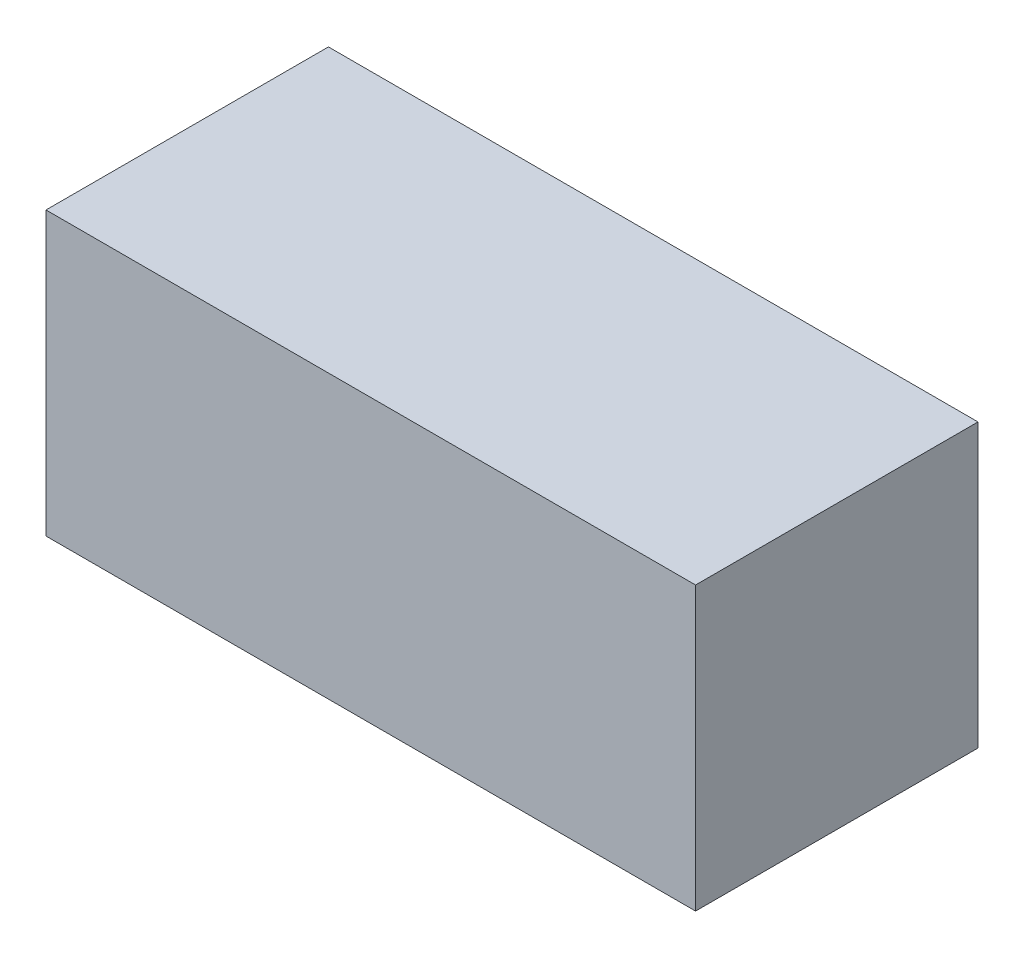
SolidWorks part; units mm, degrees
ref_plane "Front Plane" through (0, 0, 0) normal (0, 0, 1) x (1, 0, 0)
ref_plane "Top Plane" through (0, 0, 0) normal (0, 1, 0) x (1, 0, 0)
ref_plane "Right Plane" through (0, 0, 0) normal (1, 0, 0) x (0, 0, -1)
sketch "Sketch1" plane through (0, 0, 0) normal (0, 0, 1) x (1, 0, 0)
  line L0 (-6.75, 15.8) -> (6.75, 15.8) construction
  line L1 (-5.75, 26.3) -> (5.75, 26.3)
  line L2 (-5.75, 26.3) -> (-5.75, 21.3)
  line L3 (-5.75, 21.3) -> (5.75, 21.3)
  line L4 (5.75, 26.3) -> (5.75, 21.3)
  line L5 (-5.75, 26.3) -> (5.75, 21.3) construction
  line L6 (-5.75, 21.3) -> (5.75, 26.3) construction
  line L7 (-6.75, 31.8) -> (-6.75, 15.8) construction
  point P0 (0, 23.8)
  point P5 (0, 0)
  point P8 (0, 15.8)
  point P11 (-6.75, 23.8)
  dimension "D1" = 11.5
  dimension "D2" = 5
extrude "Boss-Extrude1" add sketch "Sketch1" along normal blind 5
